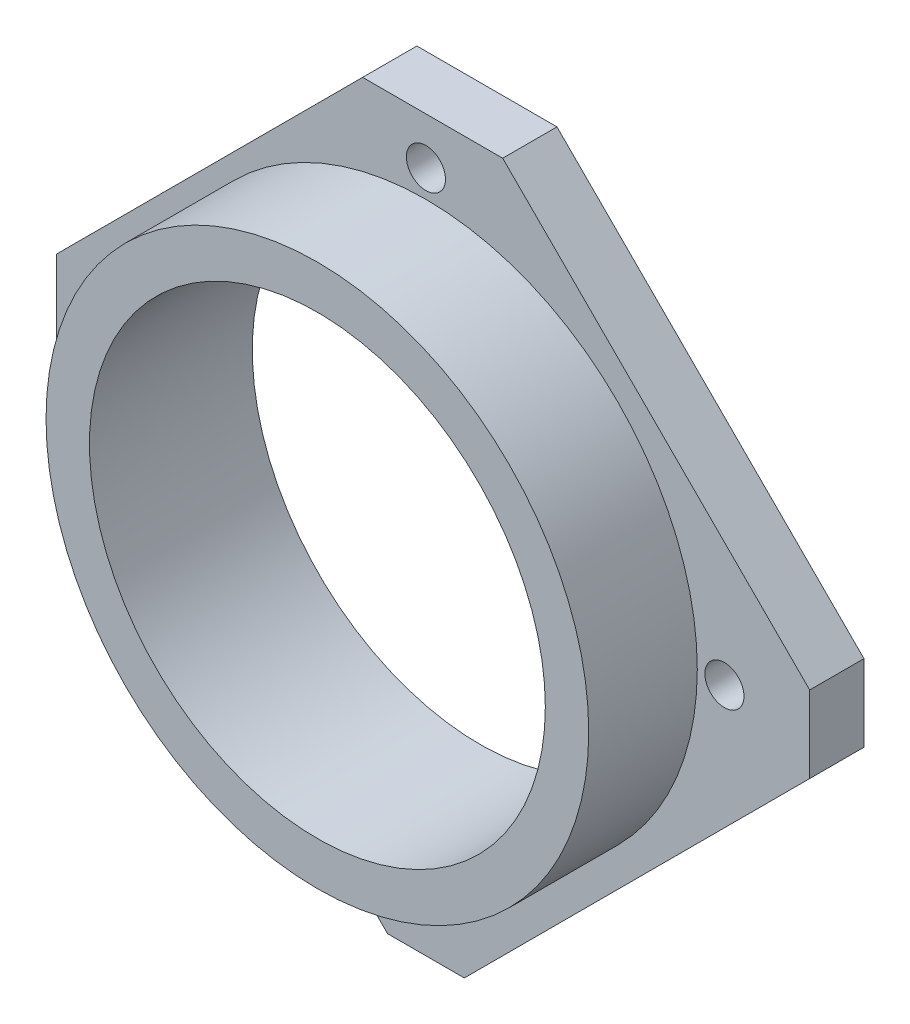
SolidWorks part; units mm, degrees
ref_plane "前视基准面" through (0, 0, 0) normal (0, 0, 1) x (1, 0, 0)
ref_plane "上视基准面" through (0, 0, 0) normal (0, 1, 0) x (1, 0, 0)
ref_plane "右视基准面" through (0, 0, 0) normal (1, 0, 0) x (0, 0, -1)
sketch "Sketch1" plane through (0, 0, 0) normal (0, 0, 1) x (1, 0, 0)
  line L0 (-3.5355, -35.3553) -> (-22.9362, -15.9547) construction
  line L1 (3.5355, -35.3553) -> (-3.5355, -35.3553) construction
  line L2 (35.3553, -3.5355) -> (3.5355, -35.3553) construction
  line L3 (35.3553, 3.5355) -> (35.3553, -3.5355) construction
  line L4 (7.0711, 31.8198) -> (35.3553, 3.5355) construction
  line L5 (7.0711, 31.8198) -> (-5.8328, 31.8198) construction
  line L6 (-3.5355, -35.3553) -> (-34.0291, -4.8618)
  line L7 (3.5355, -35.3553) -> (-3.5355, -35.3553)
  line L8 (35.3553, -3.5355) -> (3.5355, -35.3553)
  line L9 (35.3553, 3.5355) -> (35.3553, -3.5355)
  line L10 (7.0711, 31.8198) -> (35.3553, 3.5355)
  line L11 (7.0711, 31.8198) -> (-5.8328, 31.8198)
  line L12 (-34.0291, 3.6235) -> (-5.8328, 31.8198)
  line L13 (-34.0291, -4.8618) -> (-34.0291, 3.6235)
  line L14 (0, 27.5) -> (27.5, 0) construction
  line L15 (0, 27.5) -> (-27.5, 0) construction
  line L16 (27.5, 0) -> (0, -27.5) construction
  line L17 (-27.5, 0) -> (0, -27.5) construction
  circle A4 centre (27.5, 0) radius 1.8
  circle A5 centre (0, -27.5) radius 1.8
  circle A7 centre (0, 27.5) radius 1.8
  circle A9 centre (0, 0) radius 21
  circle A10 centre (-27.5, 0) radius 1.8
  point P1 (-38.2717, -0.6191)
  dimension "D1" = 42
  dimension "D2" = 3.6
  dimension "D3" = 3.6
  dimension "D5" = 3.6
  dimension "D6" = 3.6
extrude "Boss-Extrude1" add sketch "Sketch1" along normal blind 5 contours L12 L13 L6 L7 L8 L9 L10 L11 A9 A7 A5 A4 region at (-18.0994, -19.4257, 0)
sketch "Sketch2" plane through (0, 0, 5) normal (0, 0, 1) x (1, 0, 0)
  circle A0 centre (0, 0) radius 21
  circle A1 centre (0, 0) radius 25
  dimension "D1" = 50
extrude "Boss-Extrude2" add sketch "Sketch2" along normal blind 10
